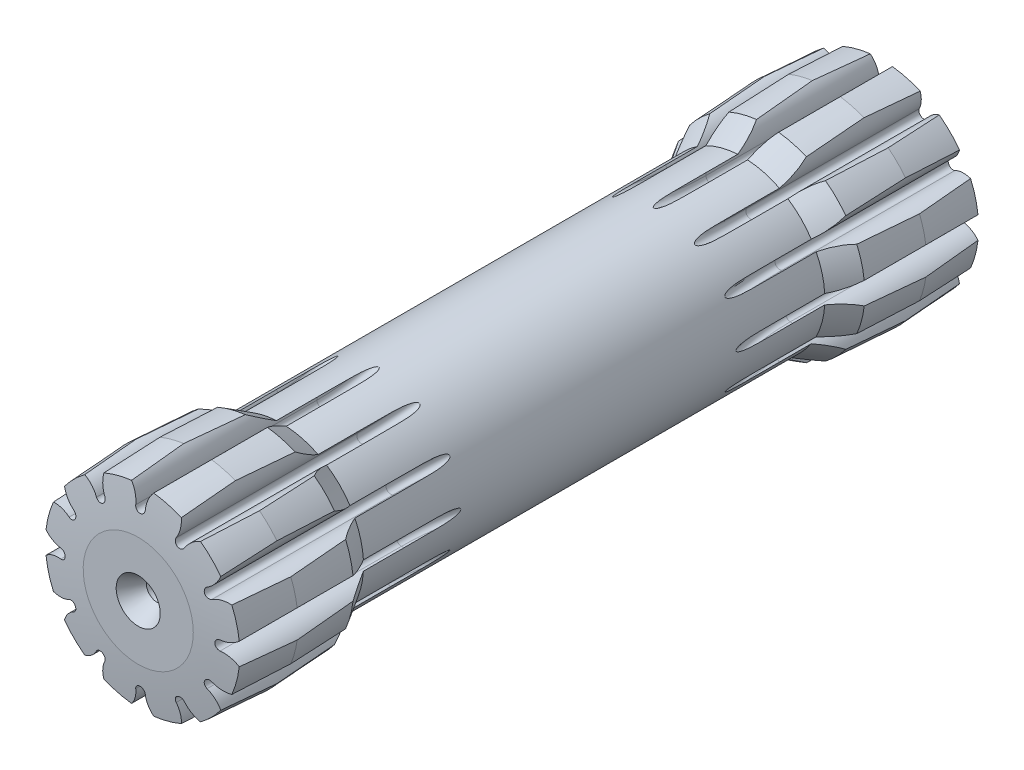
SolidWorks part; units mm, degrees
material "AISI 1045"
ref_plane "Front Plane" through (0, 0, 0) normal (0, 0, 1) x (1, 0, 0)
ref_plane "Top Plane" through (0, 0, 0) normal (0, 1, 0) x (1, 0, 0)
ref_plane "Right Plane" through (0, 0, 0) normal (1, 0, 0) x (0, 0, -1)
sketch "Sketch1" plane through (0, 0, 0) normal (1, 0, 0) x (0, 0, -1)
  line L0 (0, 0) -> (118.4245, 0) construction
  line L1 (0.6001, 13.25) -> (8.1, 13.69)
  line L2 (8.1, 13.69) -> (16.1, 13.25)
  line L3 (19.5, 11.2) -> (82.35, 11.2)
  line L4 (82.35, 11.2) -> (85.75, 13.25)
  line L5 (85.75, 13.25) -> (93.75, 13.69)
  line L6 (101.85, 0) -> (101.85, 7.5)
  line L7 (0, 0) -> (0, 7.5)
  line L8 (0, 0) -> (101.85, 0)
  line L9 (16.1, 13.25) -> (19.5, 11.2)
  line L11 (93.75, 13.69) -> (101.2499, 13.25)
  arc A0 (0, 7.5) -> (0.6001, 13.25) centre (99.7184, 0) cw
  arc A1 (101.85, 7.5) -> (101.2499, 13.25) centre (2.1316, 0) ccw
  dimension "D7" = 100
  dimension "D8" = 15
  dimension "D10" = 100
  dimension "D12" = 16.1
  dimension "D2" = 8.1
  dimension "D3" = 16.1
  dimension "D4" = 8.1
  dimension "D5" = 19.5
  dimension "D6" = 22.4
  dimension "D9" = 101.85
  dimension "D11" = 15
  dimension "D13" = 27.38
  dimension "D14" = 19.5
  dimension "D15" = 26.5
revolve "Revolve1" add sketch "Sketch1" angle 360 about L0
sketch "Sketch2" plane through (0, 0, 0) normal (1, 0, 0) x (0, 0, -1)
  line L0 (101.85, 3) -> (99.2519, 1.5)
  line L1 (99.2519, 1.5) -> (96.7513, 1.5)
  line L2 (96.7513, 1.5) -> (95.85, 0)
  line L3 (0, 0) -> (41.5, 0) construction
  line L4 (101.85, -7.5) -> (101.85, 7.5) construction
  line L5 (101.85, 3) -> (101.85, 0)
  line L6 (95.85, 0) -> (101.85, 0)
  dimension "D1" = 3
  dimension "D2" = 30
  dimension "D3" = 59
  dimension "D4" = 6
  dimension "D5" = 6
revolve "Cut-Revolve1" cut sketch "Sketch2" angle 360 about L3
sketch "Sketch3" plane through (0, 0, 0) normal (1, 0, 0) x (0, 0, -1)
  line L0 (0, 3) -> (2.5981, 1.5)
  line L1 (2.5981, 1.5) -> (5.0987, 1.5)
  line L2 (5.0987, 1.5) -> (6, 0)
  line L3 (0, 3) -> (0, 0)
  line L4 (0, 0) -> (12.7492, 0) construction
  line L5 (6, 0) -> (0, 0)
  dimension "D1" = 6
  dimension "D2" = 30
  dimension "D3" = 59
  dimension "D4" = 3
  dimension "D5" = 6
revolve "Cut-Revolve2" cut sketch "Sketch3" angle 360 about L4
ref_plane "Plane1" through (0, 0, -103) normal (0, 0, 1) x (1, 0, 0)
sketch "Sketch4" plane through (0, 0, -103) normal (0, 0, 1) x (1, 0, 0)
  line L0 (0, 0) -> (-15.7466, 0) construction
  line L1 (0, 0) -> (0, 14.7663) construction
  arc A0 (-0.65, 10.85) -> (0.65, 10.85) centre (0, 10.85) ccw
  arc A2 (1.9, 13.5575) -> (-1.9, 13.5575) centre (0, 0) ccw
  arc A3 (-1.9, 13.5575) -> (-0.65, 10.85) centre (-4.2072, 10.85) cw
  arc A4 (1.9, 13.5575) -> (0.65, 10.85) centre (4.2072, 10.85) ccw
  circle A5 centre (0, 0) radius 13.69 construction
  dimension "D1" = 1.3
  dimension "D3" = 20.4
  dimension "D2" = 3.8
extrude "Cut-Extrude1" cut sketch "Sketch4" along normal blind 25
sketch "Sketch6" plane through (0, 0, -78) normal (0, 0, -1) x (-1, 0, 0)
  line L0 (-1.5057, 13.1642) -> (-1.5057, 15.404)
  line L1 (-1.5057, 15.404) -> (1.5057, 15.404)
  line L2 (1.5057, 15.404) -> (1.5057, 13.1642)
  line L3 (-8.4949, 40.85) -> (13.6472, 40.85) construction
  arc A0 (-0.65, 10.85) -> (-1.5057, 13.1642) centre (-4.2072, 10.85) ccw construction
  arc A1 (-0.65, 10.85) -> (0.65, 10.85) centre (0, 10.85) ccw construction
  arc A2 (1.5057, 13.1642) -> (0.65, 10.85) centre (4.2072, 10.85) ccw construction
  arc A3 (-0.65, 10.85) -> (-1.5057, 13.1642) centre (-4.2072, 10.85) ccw
  arc A4 (-0.65, 10.85) -> (0.65, 10.85) centre (0, 10.85) ccw
  arc A5 (1.5057, 13.1642) -> (0.65, 10.85) centre (4.2072, 10.85) ccw
  dimension "D1" = 30
revolve "Cut-Revolve3" cut sketch "Sketch6" angle 360 about L3
ref_axis "Axis1" through (0, 0, -82.35) along (0, 0, 1)
pattern_circular "CirPattern1" count 12 over 360 about axis through (0, 0, -82.35) along (0, 0, 1) of "Cut-Extrude1", "Cut-Revolve3"
sketch "Sketch5" plane through (0, 0, 0) normal (0, 0, 1) x (1, 0, 0)
  line L0 (0, 0) -> (20.7288, 0) construction
  line L1 (0, 0) -> (0, 13.7027) construction
  line L2 (-3, 14.1961) -> (-3, 15.1961)
  line L3 (-3, 15.1961) -> (3, 15.1961)
  line L4 (3, 14.1961) -> (3, 15.1961)
  arc A2 (-0.65, 10.85) -> (0.65, 10.85) centre (0, 10.85) ccw
  arc A3 (3, 14.1961) -> (0.65, 10.85) centre (4.2072, 10.85) ccw
  arc A4 (-3, 14.1961) -> (-0.65, 10.85) centre (-4.2072, 10.85) cw
  arc A5 (-0.65, 10.85) -> (0.65, 10.85) centre (0, 10.85) ccw construction
  arc A6 (-0.65, 10.85) -> (-1.5057, 13.1642) centre (-4.2072, 10.85) ccw construction
  dimension "D1" = 6
extrude "Cut-Extrude2" cut sketch "Sketch5" against normal blind 25
sketch "Sketch8" plane through (0, 0, -25) normal (0, 0, 1) x (1, 0, 0)
  line L0 (-13.6472, 40.85) -> (11.7246, 40.85) construction
  line L1 (1.5057, 13.1642) -> (1.5057, 15.404) construction
  line L2 (1.5057, 15.404) -> (-1.5057, 15.404) construction
  line L3 (-1.5057, 15.404) -> (-1.5057, 13.1642) construction
  line L4 (1.5057, 13.1642) -> (1.5057, 15.404)
  line L5 (1.5057, 15.404) -> (-1.5057, 15.404)
  line L6 (-1.5057, 15.404) -> (-1.5057, 13.1642)
  arc A0 (-0.65, 10.85) -> (-1.5057, 13.1642) centre (-4.2072, 10.85) ccw construction
  arc A1 (1.5057, 13.1642) -> (0.65, 10.85) centre (4.2072, 10.85) ccw construction
  arc A2 (-0.65, 10.85) -> (0.65, 10.85) centre (0, 10.85) ccw construction
  arc A3 (-0.65, 10.85) -> (-1.5057, 13.1642) centre (-4.2072, 10.85) ccw
  arc A4 (1.5057, 13.1642) -> (0.65, 10.85) centre (4.2072, 10.85) ccw
  arc A5 (-0.65, 10.85) -> (0.65, 10.85) centre (0, 10.85) ccw
revolve "Cut-Revolve5" cut sketch "Sketch8" angle 360 about L0
pattern_circular "CirPattern2" count 12 over 360 about axis through (0, 0, -82.35) along (0, 0, 1) of "Cut-Extrude2", "Cut-Revolve5"
